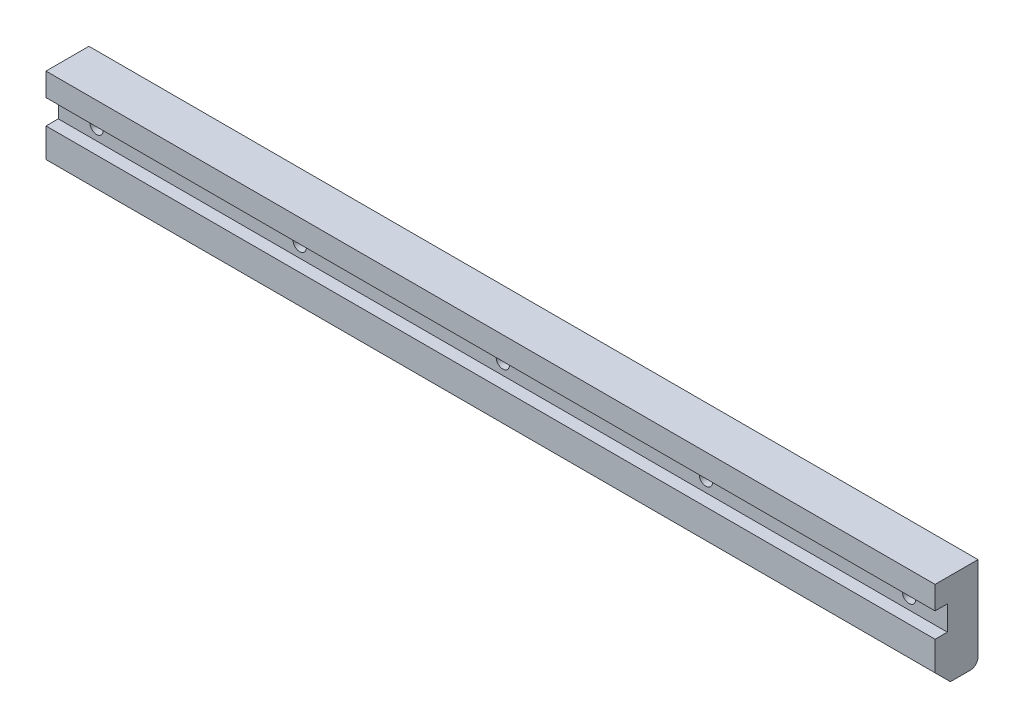
SolidWorks part; units mm, degrees
ref_plane "前基準面" through (0, 0, 0) normal (0, 0, 1) x (1, 0, 0)
ref_plane "上基準面" through (0, 0, 0) normal (0, 1, 0) x (1, 0, 0)
ref_plane "右基準面" through (0, 0, 0) normal (1, 0, 0) x (0, 0, -1)
ref_plane "平面1"
sketch "草圖1" plane through (0, 0, 0) normal (1, 0, 0) x (0, 1, 0)
  line L0 (0, 0) -> (60, 0)
  line L1 (60, 0) -> (60, 28)
  line L2 (60, 28) -> (45, 28)
  line L3 (45, 28) -> (45, 20)
  line L4 (45, 20) -> (29, 20)
  line L5 (29, 20) -> (29, 28)
  line L6 (29, 28) -> (10, 28)
  line L7 (10, 28) -> (0, 18)
  line L8 (0, 18) -> (0, 0)
  dimension "D1" = 60
  dimension "D2" = 28
  dimension "D3" = 15
  dimension "D4" = 8
  dimension "D5" = 16
  dimension "D6" = 8
  dimension "D7" = 19
  dimension "D8" = 135
extrude "擠出1" add sketch "草圖1" along normal blind 290 and the other way blind 290
hole_wizard "孔1" positions "草圖3" profile "草圖2" legacy
sketch "草圖3" plane through (0, 0, 20) normal (0, 0, 1) x (1, 0, 0)
  point P1 (-265, 37)
sketch "草圖2" plane through (-265, 37, 20) normal (1, 0, 0) x (0, -1, 0)
  line L0 (0, 0) -> (0, 52.5978)
  line L1 (0, 52.5978) -> (4.3235, 50)
  line L2 (4.3235, 50) -> (4.3235, 0)
  line L4 (4.3235, 0) -> (0, 0)
  line L6 (0, 52.5978) -> (-4.3235, 50) construction
  line L7 (0, -4.2442) -> (0, 117.3081) construction
  dimension "直徑" = 8.647
  dimension "深度" = 50
  dimension "導頭角度" = 118
cosmetic thread "裝飾螺紋線1" parameters "D1"=20, "D2"=10.34
ref_plane "平面2" through (0, 0, 0) normal (0, -1, 0) x (-1, 0, 0)
ref_plane "平面3" through (0, 0, 0) normal (0, 0, 1) x (1, 0, 0)
ref_axis "基準軸1" through (-80.9, 0, 0) along (1, 0, 0)
pattern_linear "矩形陣列1" count 5 spacing 132.5 along (1, 0, 0) of "孔1"
fillet "圓角1" radius 5 1 edges at (0, 0, 0)
